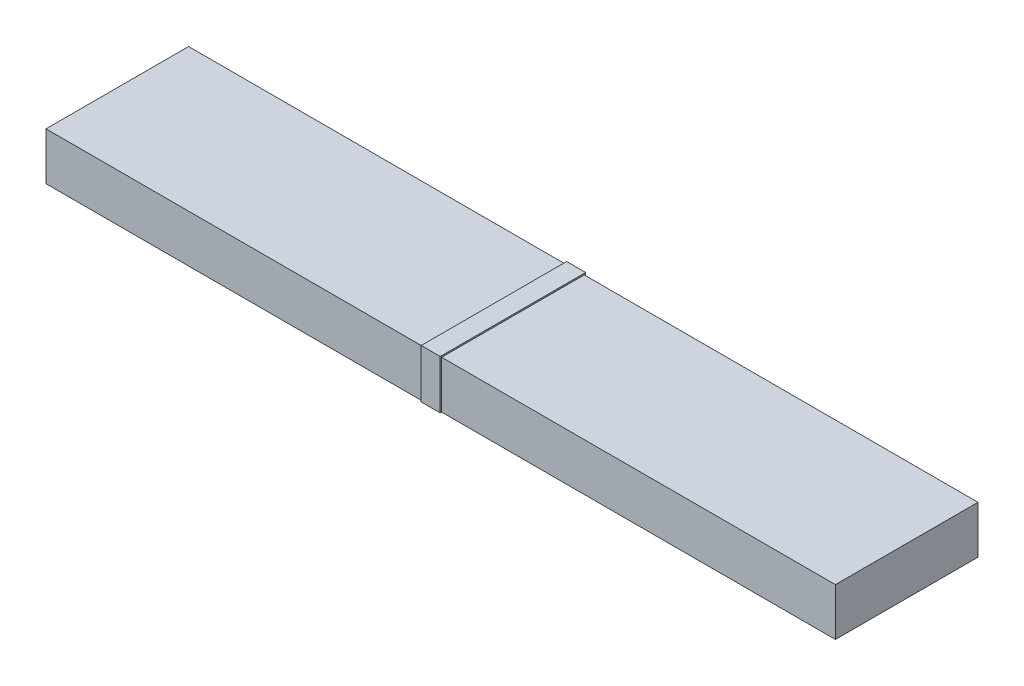
SolidWorks part; units mm, degrees
ref_plane "Front Plane" through (0, 0, 0) normal (0, 0, 1) x (1, 0, 0)
ref_plane "Top Plane" through (0, 0, 0) normal (0, 1, 0) x (1, 0, 0)
ref_plane "Right Plane" through (0, 0, 0) normal (1, 0, 0) x (0, 0, -1)
sketch "Sketch1" plane through (0, 0, 0) normal (0, 0, 1) x (1, 0, 0)
  line L1 (-830.5, -50) -> (830.5, -50)
  line L2 (-830.5, -50) -> (-830.5, 50)
  line L3 (-830.5, 50) -> (830.5, 50)
  line L4 (830.5, -50) -> (830.5, 50)
  line L5 (-830.5, -50) -> (830.5, 50) construction
  line L6 (-830.5, 50) -> (830.5, -50) construction
  point P0 (0, 0)
  dimension "D1" = 1661
  dimension "D2" = 100
extrude "Boss-Extrude1" add sketch "Sketch1" along normal blind 150 and the other way blind 150
sketch "Sketch2" plane through (0, 0, 0) normal (1, 0, 0) x (0, 0, -1)
  line L0 (-150, -50) -> (-150, 50)
  line L1 (-150, 50) -> (150, 50)
  line L2 (150, 50) -> (150, -50)
  line L3 (-153, -50) -> (-153, 53)
  line L4 (-153, 53) -> (153, 53)
  line L5 (153, 53) -> (153, -50)
  line L6 (-150, -50) -> (-153, -50)
  line L7 (150, -50) -> (153, -50)
  line L8 (-150, -50) -> (-150, 50) construction
  line L9 (150, -50) -> (-150, -50) construction
  line L10 (150, -50) -> (150, 50) construction
  line L11 (150, 50) -> (-150, 50) construction
  dimension "D2" = 0
  dimension "D3" = 0
  dimension "D4" = 0
  dimension "D5" = 0
  dimension "D6" = 0
  dimension "D1" = 3
extrude "Boss-Extrude2" add sketch "Sketch2" along normal blind 2 and the other way blind 38 separate body
